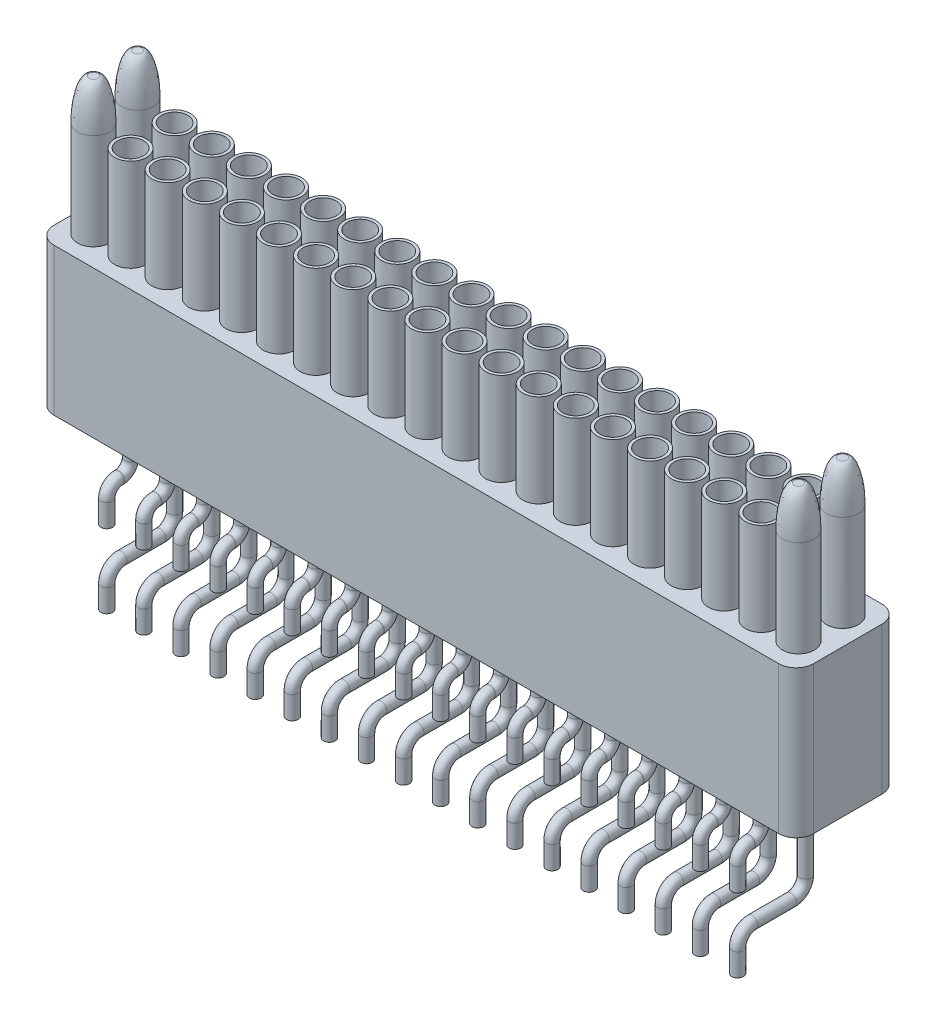
SolidWorks part; units mm, degrees
ref_plane "Front Plane" through (0, 0, 0) normal (0, 0, 1) x (1, 0, 0)
ref_plane "Top Plane" through (0, 0, 0) normal (0, 1, 0) x (1, 0, 0)
ref_plane "Right Plane" through (0, 0, 0) normal (1, 0, 0) x (0, 0, -1)
sketch "Sketch1" plane through (0, 0, 0) normal (0, 0, 1) x (1, 0, 0)
  line L1 (-6.55, -1.27) -> (6.55, -1.27)
  line L2 (-6.55, -1.27) -> (-6.55, 1.27)
  line L3 (-6.55, 1.27) -> (6.55, 1.27)
  line L4 (6.55, -1.27) -> (6.55, 1.27)
  line L5 (-6.55, -1.27) -> (6.55, 1.27) construction
  line L6 (-6.55, 1.27) -> (6.55, -1.27) construction
  point P0 (0, 0)
  dimension "D1" = 13.1
  dimension "D2" = 2.54
extrude "Boss-Extrude1" add sketch "Sketch1" along normal blind 1.78 contours L3 L4 L1 L2
sketch "Sketch2" plane through (0, 1.27, 0) normal (0, 1, 0) x (1, 0, 0)
  line L0 (-6.55, -0.89) -> (6.55, -0.89) construction
  line L1 (-6.55, -1.78) -> (-6.55, 0) construction
  line L2 (6.55, -1.78) -> (6.55, 0) construction
  line L3 (0, 0) -> (0, -1.78) construction
  line L4 (-6.55, -1.78) -> (6.55, -1.78) construction
  circle A0 centre (-0.32, -0.51) radius 0.275
  circle A1 centre (-0.32, -0.51) radius 0.225
  dimension "D3" = 0.55
  dimension "D4" = 0.05
  dimension "D1" = 0.38
  dimension "D2" = 0.32
extrude "Boss-Extrude2" add sketch "Sketch2" along normal blind 1.6
pattern_linear "LPattern1" count 10 spacing 0.64 along (1, 0, 0) count 2 spacing 0.76 along (0, 0, 1) of "Boss-Extrude2"
pattern_linear "LPattern2" count 9 spacing 0.64 along (-1, 0, 0) count 2 spacing 0.76 along (0, 0, 1) of "Boss-Extrude2"
ref_point "Point1"
ref_plane "Plane1" through (-5.44, 0, 0) normal (-1, 0, 0) x (0, 0, 1)
sketch "Sketch3" plane through (-5.44, 0, 0) normal (-1, 0, 0) x (0, 0, 1)
  line L0 (0.51, -1.27) -> (0.51, -2.92)
  line L1 (1.78, -1.27) -> (0, -1.27) construction
  line L2 (0.76, -3.17) -> (1.43, -3.17)
  line L3 (1.68, -3.42) -> (1.68, -3.81)
  line L4 (1.78, 1.27) -> (0, 1.27) construction
  line L6 (1.78, -1.27) -> (1.78, 1.27) construction
  arc A0 (1.43, -3.17) -> (1.68, -3.42) centre (1.43, -3.42) cw
  arc A1 (0.51, -2.92) -> (0.76, -3.17) centre (0.76, -2.92) ccw
  point P13 (1.68, -3.17)
  dimension "D4" = 0.25
  dimension "D1" = 0.64
  dimension "D2" = 5.08
  dimension "D3" = 0.1
sketch "Sketch4" plane through (0, -1.27, 0) normal (0, -1, 0) x (1, 0, 0)
  circle A0 centre (-5.44, 0.51) radius 0.1
  dimension "D1" = 0.2
sweep "Sweep2" add profiles "Sketch4" path "Sketch3"
ref_point "Point3"
sketch "Sketch6" plane through (-5.44, 0, 0) normal (-1, 0, 0) x (0, 0, 1)
  line L0 (1.2713, -1.27) -> (1.2713, -1.7482)
  line L1 (1.78, -1.27) -> (0, -1.27) construction
  line L2 (1.4713, -1.9482) -> (1.48, -1.9482)
  line L3 (1.68, -2.1482) -> (1.68, -2.54)
  line L4 (1.78, 1.27) -> (0, 1.27) construction
  arc A0 (1.48, -1.9482) -> (1.68, -2.1482) centre (1.48, -2.1482) cw
  arc A1 (1.2713, -1.7482) -> (1.4713, -1.9482) centre (1.4713, -1.7482) ccw
  dimension "D2" = 0.2
  dimension "D1" = 3.81
sketch "Sketch7" plane through (0, -1.27, 0) normal (0, -1, 0) x (-1, 0, 0)
  circle A0 centre (5.44, -1.2713) radius 0.1
  dimension "D1" = 0.2
sweep "Sweep3" add profiles "Sketch7" path "Sketch6"
pattern_linear "LPattern3" count 18 spacing 0.64 along (1, 0, 0) of "Sweep2", "Sweep3"
sketch "Sketch8" plane through (0, 1.27, 0) normal (0, 1, 0) x (1, 0, 0)
  line L0 (5.44, -0.51) -> (6.55, -0.51) construction
  line L1 (6.55, -1.78) -> (6.55, 0) construction
  circle A0 centre (6.08, -0.51) radius 0.275
  dimension "D2" = 0.55
  dimension "D1" = 0.64
extrude "Boss-Extrude3" add sketch "Sketch8" along normal blind 2.36 contours A0
fillet "Fillet1" radius 0.7 1 edges at (6.08, 3.63, 0.785) second distance 0.2 first distance on face at (6.08, 3.63, 0.785)
pattern_linear "LPattern5" count 2 spacing 12.16 along (-1, 0, 0) count 2 spacing 0.76 along (0, 0, 1) of "Fillet1", "Boss-Extrude3"
fillet "Fillet2" radius 0.3 4 edges at (6.55, 0, 1.78) (-6.55, 0, 1.78) (6.55, 0, 0) (-6.55, 0, 0)
